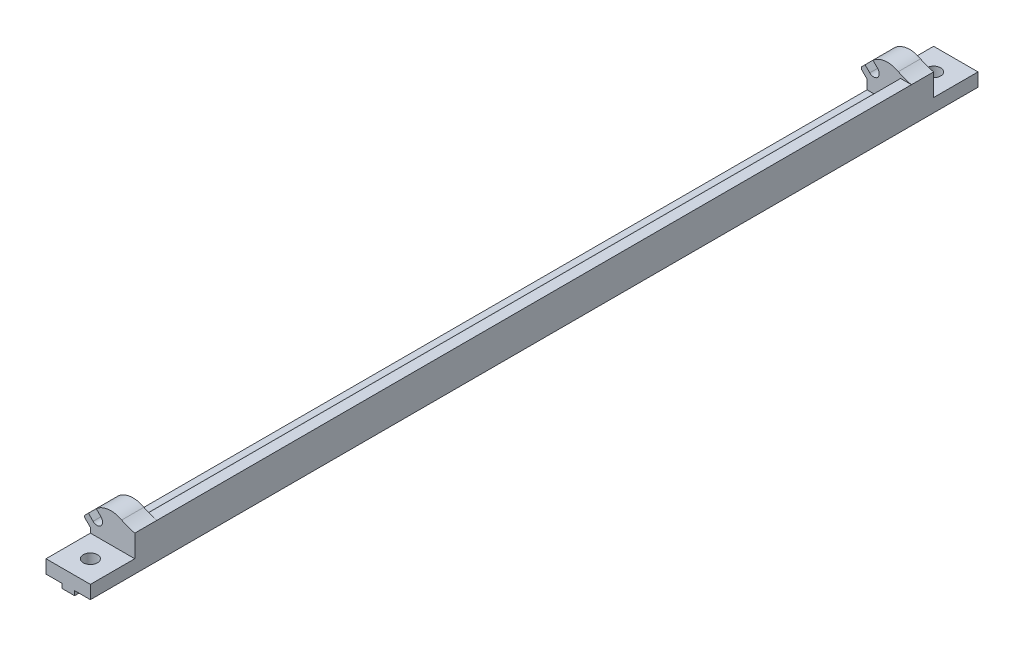
SolidWorks part; units mm, degrees
ref_plane "Front Plane" through (0, 0, 0) normal (0, 0, 1) x (1, 0, 0)
ref_plane "Top Plane" through (0, 0, 0) normal (0, 1, 0) x (1, 0, 0)
ref_plane "Right Plane" through (0, 0, 0) normal (1, 0, 0) x (0, 0, -1)
ref_plane "Plane2" through (0, 3, 0) normal (0, 1, 0) x (1, 0, 0)
sketch "Sketch1" plane through (0, 0, 0) normal (0, 0, 1) x (1, 0, 0)
  line L0 (0, 0) -> (3.55, 0)
  line L1 (3.55, 0) -> (3.55, -1)
  line L2 (3.55, -1) -> (6.45, -1)
  line L3 (6.45, -1) -> (6.45, 0)
  line L4 (6.45, 0) -> (10, 0)
  line L5 (10, 0) -> (10, 8)
  line L6 (0, 0) -> (0, 2)
  line L7 (1.5, 2) -> (0, 2)
  line L8 (5.3971, 4.25) -> (7.5622, 8)
  line L9 (7.5622, 8) -> (10, 8)
  line L10 (1.5, 6.5) -> (5.3971, 4.25) construction
  circle A0 centre (1.5, 6.5) radius 3 construction
  arc A1 (5.3971, 4.25) -> (1.5, 2) centre (1.5, 6.5) cw
  dimension "D2" = 6
  dimension "D10" = 4.5
  dimension "D1" = 2.9
  dimension "D3" = 8
  dimension "D4" = 10
  dimension "D5" = 1
  dimension "D6" = 1.5
  dimension "D7" = 6.5
  dimension "D8" = 240
  dimension "D9" = 2.4378
  dimension "D11" = 2
extrude "Main" add sketch "Sketch1" along normal blind 100
ref_plane "Plane1" through (0, 0, 90) normal (0, 0, 1) x (1, 0, 0)
sketch "Sketch3" plane through (0, 0, 90) normal (0, 0, 1) x (1, 0, 0)
  line L0 (-1.5052, 5.6161) -> (0, 4.1109)
  line L1 (-0.4445, 6.6768) -> (-1.5052, 5.6161)
  line L2 (1.3232, 8.4445) -> (4.2204, 11.3417)
  line L3 (4.2204, 11.3417) -> (7.5622, 8)
  line L4 (-0.4445, 6.6768) -> (0.6161, 5.6161)
  line L5 (1.3232, 8.4445) -> (2.3839, 7.3839)
  line L7 (0, 0) -> (10, 0)
  line L8 (10, 0) -> (10, 8)
  line L9 (7.5622, 8) -> (10, 8)
  line L11 (0, 4.1109) -> (0, 0)
  arc A0 (0.6161, 5.6161) -> (2.3839, 7.3839) centre (1.5, 6.5) ccw
  circle A1 centre (1.5, 6.5) radius 3 construction
  point P12 (0, 4.1472)
  point P17 (0, 0)
  dimension "D1" = 1.25
  dimension "D2" = 1.5
  dimension "D3" = 1.5
  dimension "D4" = 135
extrude "FixForRollingCylinder" add sketch "Sketch3" against normal blind 5
sketch "Sketch4" plane through (0, 3, 0) normal (0, 1, 0) x (1, 0, 0)
  line L1 (0, -90) -> (10, -90)
  line L2 (0, -90) -> (0, -100)
  line L3 (0, -100) -> (10, -100)
  line L4 (10, -90) -> (10, -100)
extrude "HorizontalCut" cut sketch "Sketch4" along normal blind 10
sketch "Sketch7" plane through (0, 3, 0) normal (0, 1, 0) x (1, 0, 0)
  line L0 (-2.2, -90) -> (2.2, -90) construction
  line L1 (0, -90) -> (10, -90)
  line L2 (0, -90) -> (0, -100)
  line L3 (0, -100) -> (10, -100)
  line L4 (10, -90) -> (10, -100)
  line L5 (10, -100) -> (10, -90) construction
  point P4 (0, -100)
  point P6 (9.9288, -90)
  point P9 (10, -90)
extrude "Boss-Extrude1" add sketch "Sketch7" against normal blind 1
sketch "Sketch5" plane through (0, 2, 0) normal (0, 1, 0) x (1, 0, 0)
  line L0 (0, -100) -> (10, -100) construction
  line L1 (10, -100) -> (10, -90) construction
  circle A0 centre (5, -95) radius 1.6
  point P3 (0, 0)
  point P7 (10.3353, -94.6938)
  dimension "D1" = 3.2
  dimension "D2" = 5
  dimension "D3" = 5
extrude "MakerBeamHole" cut sketch "Sketch5" along normal through all both and the other way through all
mirror "Mirror1" about plane through (0, 0, 0) normal (0, 0, 1) of bodies 104
fillet "Fillet1" radius 10 2 edges at (7.5622, 8, -87.5) (7.5622, 8, 87.5)
fillet "Fillet2" radius 5 2 edges at (4.2204, 11.3417, -87.5) (4.2204, 11.3417, 87.5)
fillet "Fillet3" radius 0.5 2 edges at (-1.5052, 5.6161, 87.5) (-1.5052, 5.6161, -87.5)
